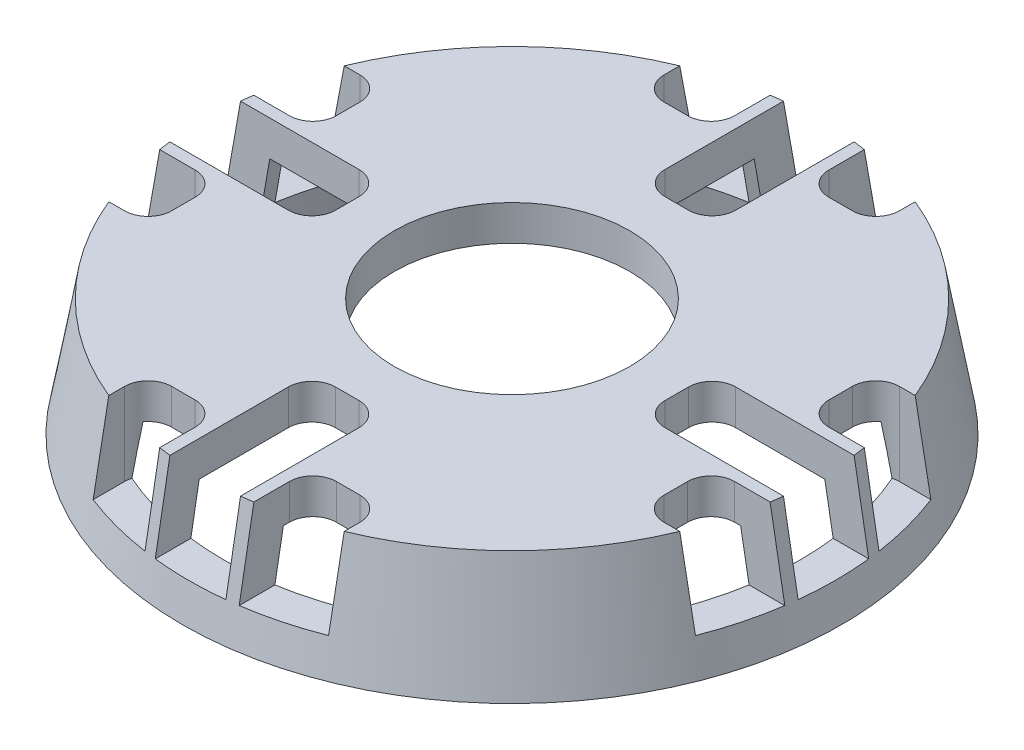
SolidWorks part; units mm, degrees
ref_plane "Front Plane" through (0, 0, 0) normal (0, 0, 1) x (1, 0, 0)
ref_plane "Top Plane" through (0, 0, 0) normal (0, 1, 0) x (1, 0, 0)
ref_plane "Right Plane" through (0, 0, 0) normal (1, 0, 0) x (0, 0, -1)
sketch "Sketch1" plane through (0, 0, 0) normal (0, 1, 0) x (1, 0, 0)
  circle A0 centre (0, 0) radius 14
  dimension "D1" = 28
extrude "Boss-Extrude1" add sketch "Sketch1" along normal blind 5 draft 10
sketch "Sketch2" plane through (0, 0, 0) normal (0, -1, 0) x (1, 0, 0)
  circle A0 centre (0, 0) radius 12.5
  dimension "D1" = 25
extrude "Cut-Extrude1" cut sketch "Sketch2" against normal blind 3.5 draft 10
sketch "Sketch3" plane through (0, 5, 0) normal (0, 1, 0) x (1, 0, 0)
  line L0 (0, 0) -> (0, 7) construction
  line L1 (0, 0) -> (0, -7) construction
  line L2 (0, 0) -> (-7, 0) construction
  line L3 (0, 0) -> (7, 0) construction
  line L4 (-7, 0) -> (-7, 1.5)
  line L5 (-7, 0) -> (-7, -1.5)
  line L6 (-7, 1.5) -> (-13.9194, 1.5)
  line L7 (-7, -1.5) -> (-13.9194, -1.5)
  line L8 (0, 7) -> (-1.5, 7)
  line L9 (0, 7) -> (1.5, 7)
  line L10 (-1.5, 7) -> (-1.5, 13.9194)
  line L11 (1.5, 7) -> (1.5, 13.9194)
  line L12 (7, 0) -> (7, 1.5)
  line L13 (7, 0) -> (7, -1.5)
  line L14 (7, 1.5) -> (13.9194, 1.5)
  line L15 (7, -1.5) -> (13.9194, -1.5)
  line L16 (0, -7) -> (1.5, -7)
  line L17 (0, -7) -> (-1.5, -7)
  line L18 (-1.5, -7) -> (-1.5, -13.9194)
  line L19 (1.5, -7) -> (1.5, -13.9194)
  line L20 (1.5, 10.4597) -> (2, 10.4597) construction
  line L21 (-1.5, 10.4597) -> (-2, 10.4597) construction
  line L22 (-2, 10.4597) -> (-2, 13.8564)
  line L23 (-2, 10.4597) -> (-5, 10.4597)
  line L24 (-5, 10.4597) -> (-5, 13.0767)
  line L25 (2, 10.4597) -> (2, 13.8564)
  line L26 (2, 10.4597) -> (5, 10.4597)
  line L27 (5, 10.4597) -> (5, 13.0767)
  line L28 (10.4597, 1.5) -> (10.4597, 2) construction
  line L29 (10.4597, -1.5) -> (10.4597, -2) construction
  line L30 (10.4597, -2) -> (13.8564, -2)
  line L31 (10.4597, -2) -> (10.4597, -5)
  line L32 (10.4597, -5) -> (13.0767, -5)
  line L33 (10.4597, 2) -> (13.8564, 2)
  line L34 (10.4597, 2) -> (10.4597, 5)
  line L35 (10.4597, 5) -> (13.0767, 5)
  line L36 (1.5, -10.4597) -> (2, -10.4597) construction
  line L37 (2, -10.4597) -> (5, -10.4597)
  line L38 (2, -10.4597) -> (2, -13.8564)
  line L39 (5, -10.4597) -> (5, -13.0767)
  line L40 (-1.5, -10.4597) -> (-2, -10.4597) construction
  line L41 (-2, -10.4597) -> (-5, -10.4597)
  line L42 (-5, -10.4597) -> (-5, -13.0767)
  line L43 (-2, -10.4597) -> (-2, -13.8564)
  line L44 (-10.4597, 1.5) -> (-10.4597, 2) construction
  line L45 (-10.4597, -1.5) -> (-10.4597, -2) construction
  line L46 (-10.4597, 2) -> (-10.4597, 5)
  line L47 (-10.4597, 5) -> (-13.0767, 5)
  line L48 (-10.4597, 2) -> (-13.8564, 2)
  line L49 (-10.4597, -2) -> (-13.8564, -2)
  line L50 (-10.4597, -2) -> (-10.4597, -5)
  line L51 (-10.4597, -5) -> (-13.0767, -5)
  circle A1 centre (0, 0) radius 14 construction
  arc A2 (13.8564, 2) -> (13.0767, 5) centre (0, 0) ccw
  arc A3 (13.9194, -1.5) -> (13.9194, 1.5) centre (0, 0) ccw
  arc A4 (13.0767, -5) -> (13.8564, -2) centre (0, 0) ccw
  arc A5 (2, -13.8564) -> (5, -13.0767) centre (0, 0) ccw
  arc A6 (-1.5, -13.9194) -> (1.5, -13.9194) centre (0, 0) ccw
  arc A7 (-5, -13.0767) -> (-2, -13.8564) centre (0, 0) ccw
  arc A8 (-13.8564, -2) -> (-13.0767, -5) centre (0, 0) ccw
  arc A9 (-13.9194, 1.5) -> (-13.9194, -1.5) centre (0, 0) ccw
  arc A10 (-13.0767, 5) -> (-13.8564, 2) centre (0, 0) ccw
  arc A11 (-2, 13.8564) -> (-5, 13.0767) centre (0, 0) ccw
  arc A12 (1.5, 13.9194) -> (-1.5, 13.9194) centre (0, 0) ccw
  arc A13 (5, 13.0767) -> (2, 13.8564) centre (0, 0) ccw
  dimension "D1" = 7
  dimension "D2" = 7
  dimension "D3" = 7
  dimension "D4" = 7
  dimension "D5" = 1.5
  dimension "D6" = 1.5
  dimension "D7" = 1.5
  dimension "D8" = 1.5
  dimension "D9" = 1.5
  dimension "D10" = 1.5
  dimension "D11" = 1.5
  dimension "D12" = 0.5
  dimension "D13" = 0.5
  dimension "D14" = 3
  dimension "D15" = 3
  dimension "D16" = 0.5
  dimension "D17" = 0.5
  dimension "D18" = 3
  dimension "D19" = 3
  dimension "D20" = 3
extrude "Cut-Extrude2" cut sketch "Sketch3" against normal blind 3.5
sketch "Sketch4" plane through (0, 5, 0) normal (0, 1, 0) x (1, 0, 0)
  line L0 (0, 7) -> (0, -7) construction
  line L1 (-1.5, 7) -> (1.5, 7) construction
  line L2 (1.5, -7) -> (-1.5, -7) construction
  circle A0 centre (0, 0) radius 5
  dimension "D1" = 10
extrude "Cut-Extrude4" cut sketch "Sketch4" against normal blind 3.5
fillet "Fillet2" radius 1 24 edges at (10.4597, 4.25, -2) (7, 4.25, 1.5) (10.4597, 4.25, 5) (10.4597, 4.25, -5) (7, 4.25, -1.5) (10.4597, 4.25, 2) (-2, 4.25, -10.4597) (1.5, 4.25, -7) (5, 4.25, -10.4597) (-5, 4.25, -10.4597) (-1.5, 4.25, -7) (2, 4.25, -10.4597) (-10.4597, 4.25, 2) (-7, 4.25, -1.5) (-10.4597, 4.25, -5) (-10.4597, 4.25, 5) (-7, 4.25, 1.5) (-10.4597, 4.25, -2) (2, 4.25, 10.4597) (-1.5, 4.25, 7) (-5, 4.25, 10.4597) (5, 4.25, 10.4597) (1.5, 4.25, 7) (-2, 4.25, 10.4597)
